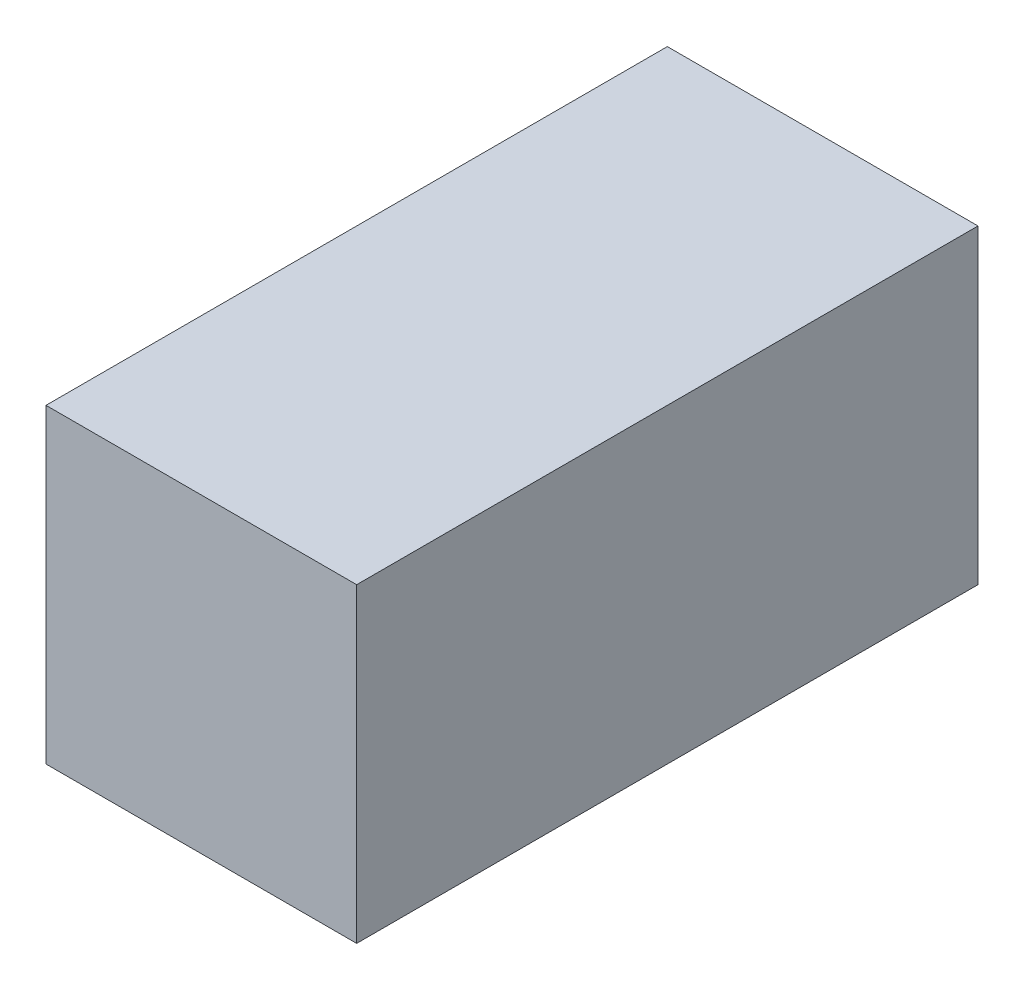
SolidWorks part; units mm, degrees
ref_plane "Front Plane" through (0, 0, 0) normal (0, 0, 1) x (1, 0, 0)
ref_plane "Top Plane" through (0, 0, 0) normal (0, 1, 0) x (1, 0, 0)
ref_plane "Right Plane" through (0, 0, 0) normal (1, 0, 0) x (0, 0, -1)
sketch "Sketch1" plane through (0, 0, 0) normal (0, 0, 1) x (1, 0, 0)
  line L1 (0, 0) -> (76.2, 0)
  line L2 (0, 0) -> (0, 76.2)
  line L3 (0, 76.2) -> (76.2, 76.2)
  line L4 (76.2, 0) -> (76.2, 76.2)
  dimension "D1" = 76.2
  dimension "D2" = 76.2
extrude "Boss-Extrude1" add sketch "Sketch1" along normal blind 152.4
ref_plane "Plane2" through (38.1, 0, 0) normal (-1, 0, 0) x (0, 0, 1)
